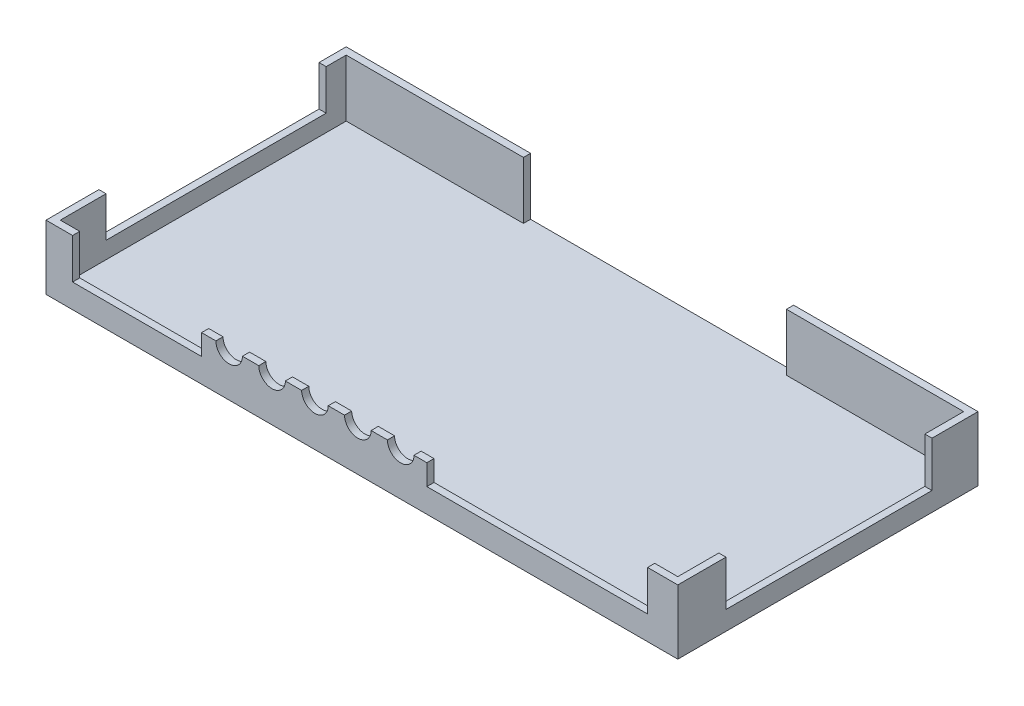
SolidWorks part; units mm, degrees
ref_plane "Front Plane" through (0, 0, 0) normal (0, 0, 1) x (1, 0, 0)
ref_plane "Top Plane" through (0, 0, 0) normal (0, 1, 0) x (1, 0, 0)
ref_plane "Right Plane" through (0, 0, 0) normal (1, 0, 0) x (0, 0, -1)
sketch "Sketch1" plane through (0, 0, 0) normal (0, 1, 0) x (1, 0, 0)
  line L0 (-110.5, -52.5) -> (-110.5, 52.5)
  line L1 (-108, -50) -> (108, -50)
  line L2 (-108, -50) -> (-108, 50)
  line L3 (-108, 50) -> (108, 50)
  line L4 (108, -50) -> (108, 50)
  line L5 (-108, -50) -> (108, 50) construction
  line L6 (-108, 50) -> (108, -50) construction
  line L7 (-110.5, 52.5) -> (110.5, 52.5)
  line L8 (110.5, -52.5) -> (110.5, 52.5)
  line L9 (-110.5, -52.5) -> (110.5, -52.5)
  point P0 (0, 0)
  dimension "D1" = 216
  dimension "D2" = 100
  dimension "D3" = 2.5
extrude "Boss-Extrude1" add sketch "Sketch1" along normal blind 20 contours L0 L9 L8 L7 L4 L1 L2 L3 region at (-108.0532, 0, 0)
extrude "Boss-Extrude2" add sketch "Sketch1<3>" against normal blind 2.5 contours L0 L7 L8 L9
sketch "Sketch1<3>" plane through (0, 0, 0) normal (0, 1, 0) x (1, 0, 0) same geometry as "Sketch1"
ref_plane "Plane1" through (-110.5, 20, 52.5) normal (1, 0, 0) x (0, 0, -1)
sketch "Sketch3" plane through (0, 0, 52.5) normal (0, 0, 1) x (1, 0, 0)
  line L0 (-110.5, 20) -> (110.5, 20) construction
  line L1 (-101.2008, 20) -> (99.9204, 20)
  line L2 (-101.2008, 20) -> (-101.2008, 5.8947)
  line L3 (-101.2008, 5.8947) -> (99.9204, 5.8947)
  line L4 (99.9204, 20) -> (99.9204, 5.8947)
extrude "Cut-Extrude1" cut sketch "Sketch3" against normal blind 10
sketch "Sketch4" plane through (110.5, 0, 0) normal (1, 0, 0) x (0, 0, -1)
  line L0 (-52.5, 20) -> (52.5, 20) construction
  line L1 (-35.6625, 20) -> (36.407, 20)
  line L2 (-35.6625, 20) -> (-35.6625, 4.1415)
  line L3 (-35.6625, 4.1415) -> (36.407, 4.1415)
  line L4 (36.407, 20) -> (36.407, 4.1415)
extrude "Cut-Extrude2" cut sketch "Sketch4" against normal blind 10
sketch "Sketch5" plane through (0, 0, 52.5) normal (0, 0, 1) x (1, 0, 0)
  line L0 (-144.165, 13.1347) -> (142.8743, 13.1347) construction
  line L1 (-101.2008, 5.8947) -> (99.9204, 5.8947) construction
  line L2 (0, -12.375) -> (0, 12.375) construction
  line L4 (-56.08, 5.8947) -> (22.72, 5.8947)
  line L6 (-41.78, 13.1347) -> (-36.08, 13.1347)
  line L7 (-26.78, 13.1347) -> (-21.08, 13.1347)
  line L8 (-11.78, 13.1347) -> (-6.08, 13.1347)
  line L9 (3.22, 13.1347) -> (8.92, 13.1347)
  line L10 (-56.08, 13.1347) -> (-56.08, 5.8947)
  line L11 (-56.08, 13.1347) -> (-51.08, 13.1347)
  line L12 (22.72, 13.1347) -> (22.72, 5.8947)
  line L13 (18.22, 13.1347) -> (22.72, 13.1347)
  circle A0 centre (-46.43, 13.1347) radius 4.65 construction
  circle A1 centre (-31.43, 13.1347) radius 4.65 construction
  circle A2 centre (-16.43, 13.1347) radius 4.65 construction
  circle A3 centre (-1.43, 13.1347) radius 4.65 construction
  circle A4 centre (13.57, 13.1347) radius 4.65 construction
  arc A5 (-51.08, 13.1347) -> (-41.78, 13.1347) centre (-46.43, 13.1347) ccw
  arc A6 (-36.08, 13.1347) -> (-26.78, 13.1347) centre (-31.43, 13.1347) ccw
  arc A7 (-21.08, 13.1347) -> (-11.78, 13.1347) centre (-16.43, 13.1347) ccw
  arc A8 (-6.08, 13.1347) -> (3.22, 13.1347) centre (-1.43, 13.1347) ccw
  arc A9 (8.92, 13.1347) -> (18.22, 13.1347) centre (13.57, 13.1347) ccw
  point P4 (-46.43, 13.1347)
  point P5 (-31.43, 13.1347)
  point P6 (-16.43, 13.1347)
  point P7 (-1.43, 13.1347)
  point P8 (13.57, 13.1347)
  dimension "D7" = 9.3
  dimension "D8" = 5
  dimension "D9" = 4.5
  dimension "D1" = 7.24
  dimension "D2" = 46.43
  dimension "D3" = 31.43
  dimension "D4" = 16.43
  dimension "D5" = 1.43
  dimension "D6" = 13.57
extrude "Boss-Extrude3" add sketch "Sketch5" against normal up to surface (2.5 mm away) up to face at (-0.3201, 11.4737, 50)
sketch "Sketch6" plane through (0, 0, -52.5) normal (0, 0, -1) x (-1, 0, 0)
  line L0 (110.5, 20) -> (-110.5, 20) construction
  line L1 (-46, 20) -> (46, 20)
  line L2 (-46, 20) -> (-46, 0)
  line L3 (-46, 0) -> (46, 0)
  line L4 (46, 20) -> (46, 0)
  line L5 (0, 12.375) -> (0, -12.375) construction
  dimension "D1" = 92
  dimension "D2" = 46
  dimension "D3" = 20
extrude "Cut-Extrude3" cut sketch "Sketch6" against normal blind 10
sketch "Sketch7" plane through (-110.5, 0, 0) normal (-1, 0, 0) x (0, 0, 1)
  line L0 (52.5, 20) -> (-52.5, 20) construction
  line L1 (34, 20) -> (-43, 20)
  line L2 (34, 20) -> (34, 5.9)
  line L3 (34, 5.9) -> (-43, 5.9)
  line L4 (-43, 20) -> (-43, 5.9)
  line L5 (52.5, 20) -> (52.5, -2.5) construction
  line L6 (52.5, -2.5) -> (-52.5, -2.5) construction
  dimension "D1" = 18.5
  dimension "D2" = 7
  dimension "D3" = 8.4
extrude "Cut-Extrude4" cut sketch "Sketch7" against normal blind 10
equation "\"D2@Sketch6\"=\"D1@Sketch6\"/2"
